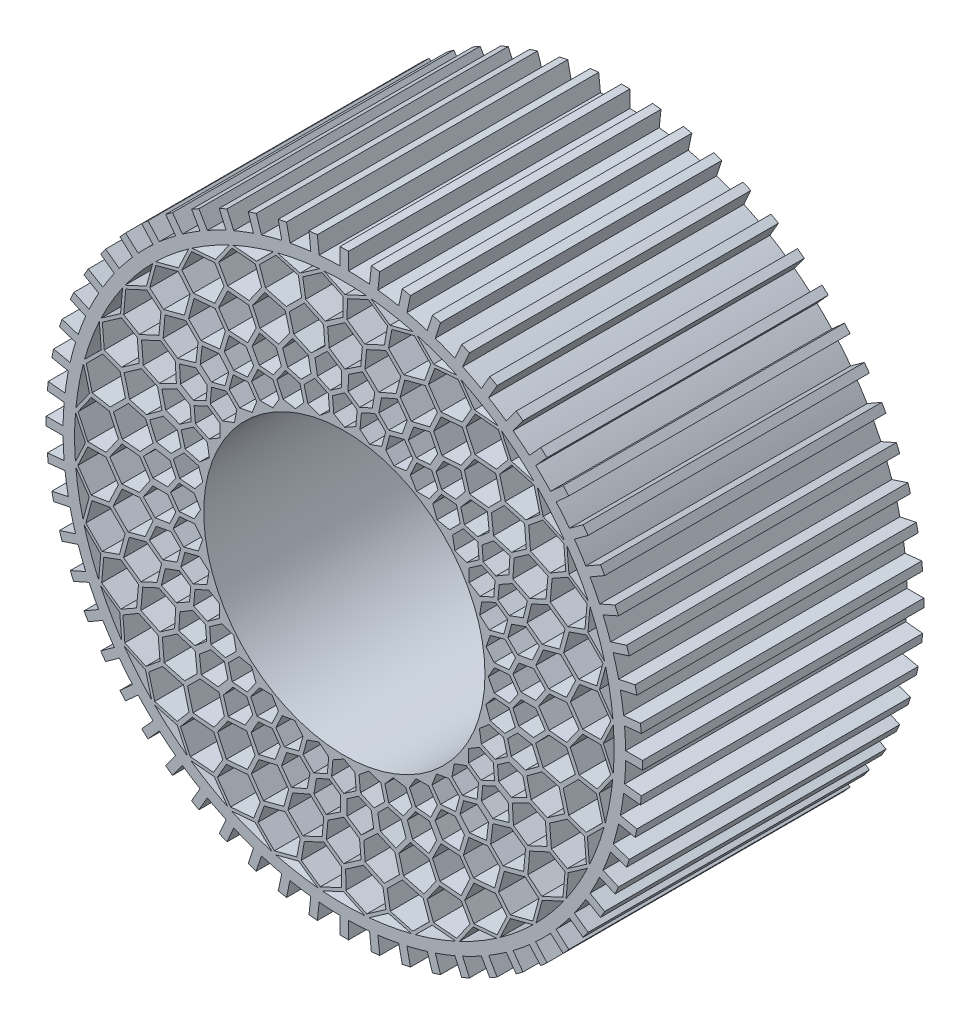
SolidWorks part; units mm, degrees
ref_plane "Front Plane" through (0, 0, 0) normal (0, 0, 1) x (1, 0, 0)
ref_plane "Top Plane" through (0, 0, 0) normal (0, 1, 0) x (1, 0, 0)
ref_plane "Right Plane" through (0, 0, 0) normal (1, 0, 0) x (0, 0, -1)
sketch "Sketch1" plane through (0, 0, 0) normal (0, 0, 1) x (1, 0, 0)
  line L0 (0, 0) -> (0, 101.6)
  line L1 (0, 101.6) -> (0, 107.696) construction
  line L2 (-1.524, 107.696) -> (1.524, 107.696)
  line L3 (1.524, 107.696) -> (1.524, 101.5886)
  line L4 (-1.524, 107.696) -> (-1.524, 101.5886)
  line L5 (10.6201, 101.0434) -> (11.2573, 107.106) construction
  line L6 (9.7416, 107.2653) -> (12.7729, 106.9467)
  line L7 (9.7416, 107.2653) -> (9.1032, 101.1914)
  line L8 (12.7729, 106.9467) -> (12.1345, 100.8728)
  line L9 (21.1238, 99.3798) -> (22.3913, 105.3426) construction
  line L10 (20.9006, 105.6594) -> (23.882, 105.0257)
  line L11 (20.9006, 105.6594) -> (19.6308, 99.6855)
  line L12 (23.882, 105.0257) -> (22.6121, 99.0518)
  line L13 (31.3961, 96.6273) -> (33.2799, 102.425) construction
  line L14 (31.8305, 102.8959) -> (34.7293, 101.954)
  line L15 (31.8305, 102.8959) -> (29.9432, 97.0874)
  line L16 (34.7293, 101.954) -> (32.842, 96.1455)
  line L17 (41.3244, 92.8162) -> (43.8039, 98.3852) construction
  line L18 (42.4117, 99.0051) -> (45.1962, 97.7653)
  line L19 (42.4117, 99.0051) -> (39.9276, 93.4256)
  line L20 (45.1962, 97.7653) -> (42.712, 92.1859)
  line L21 (50.8, 87.9882) -> (53.848, 93.2675) construction
  line L22 (52.5282, 94.0295) -> (55.1678, 92.5055)
  line L23 (52.5282, 94.0295) -> (49.4745, 88.7403)
  line L24 (55.1678, 92.5055) -> (52.1141, 87.2163)
  line L25 (59.719, 82.1961) -> (63.3021, 87.1279) construction
  line L26 (62.0692, 88.0237) -> (64.5351, 86.2321)
  line L27 (62.0692, 88.0237) -> (58.4793, 83.0827)
  line L28 (64.5351, 86.2321) -> (60.9452, 81.2911)
  line L29 (67.9837, 75.5035) -> (72.0627, 80.0337) construction
  line L30 (70.9301, 81.0535) -> (73.1952, 79.014)
  line L31 (70.9301, 81.0535) -> (66.8435, 76.5148)
  line L32 (73.1952, 79.014) -> (69.1086, 74.4753)
  line L33 (75.5035, 67.9837) -> (80.0337, 72.0627) construction
  line L34 (79.014, 73.1952) -> (81.0535, 70.9301)
  line L35 (79.014, 73.1952) -> (74.4753, 69.1086)
  line L36 (81.0535, 70.9301) -> (76.5148, 66.8435)
  line L37 (82.1961, 59.719) -> (87.1279, 63.3021) construction
  line L38 (86.2321, 64.5351) -> (88.0237, 62.0692)
  line L39 (86.2321, 64.5351) -> (81.2911, 60.9452)
  line L40 (88.0237, 62.0692) -> (83.0827, 58.4793)
  line L41 (87.9882, 50.8) -> (93.2675, 53.848) construction
  line L42 (92.5055, 55.1678) -> (94.0295, 52.5282)
  line L43 (92.5055, 55.1678) -> (87.2163, 52.1141)
  line L44 (94.0295, 52.5282) -> (88.7403, 49.4745)
  line L45 (92.8162, 41.3244) -> (98.3852, 43.8039) construction
  line L46 (97.7653, 45.1962) -> (99.0051, 42.4117)
  line L47 (97.7653, 45.1962) -> (92.1859, 42.712)
  line L48 (99.0051, 42.4117) -> (93.4256, 39.9276)
  line L49 (96.6273, 31.3961) -> (102.425, 33.2799) construction
  line L50 (101.954, 34.7293) -> (102.8959, 31.8305)
  line L51 (101.954, 34.7293) -> (96.1455, 32.842)
  line L52 (102.8959, 31.8305) -> (97.0874, 29.9432)
  line L53 (99.3798, 21.1238) -> (105.3426, 22.3913) construction
  line L54 (105.0257, 23.882) -> (105.6594, 20.9006)
  line L55 (105.0257, 23.882) -> (99.0518, 22.6121)
  line L56 (105.6594, 20.9006) -> (99.6855, 19.6308)
  line L57 (101.0434, 10.6201) -> (107.106, 11.2573) construction
  line L58 (106.9467, 12.7729) -> (107.2653, 9.7416)
  line L59 (106.9467, 12.7729) -> (100.8728, 12.1345)
  line L60 (107.2653, 9.7416) -> (101.1914, 9.1032)
  line L61 (101.6, 0) -> (107.696, 0) construction
  line L62 (107.696, 1.524) -> (107.696, -1.524)
  line L63 (107.696, 1.524) -> (101.5886, 1.524)
  line L64 (107.696, -1.524) -> (101.5886, -1.524)
  line L65 (101.0434, -10.6201) -> (107.106, -11.2573) construction
  line L66 (107.2653, -9.7416) -> (106.9467, -12.7729)
  line L67 (107.2653, -9.7416) -> (101.1914, -9.1032)
  line L68 (106.9467, -12.7729) -> (100.8728, -12.1345)
  line L69 (99.3798, -21.1238) -> (105.3426, -22.3913) construction
  line L70 (105.6594, -20.9006) -> (105.0257, -23.882)
  line L71 (105.6594, -20.9006) -> (99.6855, -19.6308)
  line L72 (105.0257, -23.882) -> (99.0518, -22.6121)
  line L73 (96.6273, -31.3961) -> (102.425, -33.2799) construction
  line L74 (102.8959, -31.8305) -> (101.954, -34.7293)
  line L75 (102.8959, -31.8305) -> (97.0874, -29.9432)
  line L76 (101.954, -34.7293) -> (96.1455, -32.842)
  line L77 (92.8162, -41.3244) -> (98.3852, -43.8039) construction
  line L78 (99.0051, -42.4117) -> (97.7653, -45.1962)
  line L79 (99.0051, -42.4117) -> (93.4256, -39.9276)
  line L80 (97.7653, -45.1962) -> (92.1859, -42.712)
  line L81 (87.9882, -50.8) -> (93.2675, -53.848) construction
  line L82 (94.0295, -52.5282) -> (92.5055, -55.1678)
  line L83 (94.0295, -52.5282) -> (88.7403, -49.4745)
  line L84 (92.5055, -55.1678) -> (87.2163, -52.1141)
  line L85 (82.1961, -59.719) -> (87.1279, -63.3021) construction
  line L86 (88.0237, -62.0692) -> (86.2321, -64.5351)
  line L87 (88.0237, -62.0692) -> (83.0827, -58.4793)
  line L88 (86.2321, -64.5351) -> (81.2911, -60.9452)
  line L89 (75.5035, -67.9837) -> (80.0337, -72.0627) construction
  line L90 (81.0535, -70.9301) -> (79.014, -73.1952)
  line L91 (81.0535, -70.9301) -> (76.5148, -66.8435)
  line L92 (79.014, -73.1952) -> (74.4753, -69.1086)
  line L93 (67.9837, -75.5035) -> (72.0627, -80.0337) construction
  line L94 (73.1952, -79.014) -> (70.9301, -81.0535)
  line L95 (73.1952, -79.014) -> (69.1086, -74.4753)
  line L96 (70.9301, -81.0535) -> (66.8435, -76.5148)
  line L97 (59.719, -82.1961) -> (63.3021, -87.1279) construction
  line L98 (64.5351, -86.2321) -> (62.0692, -88.0237)
  line L99 (64.5351, -86.2321) -> (60.9452, -81.2911)
  line L100 (62.0692, -88.0237) -> (58.4793, -83.0827)
  line L101 (50.8, -87.9882) -> (53.848, -93.2675) construction
  line L102 (55.1678, -92.5055) -> (52.5282, -94.0295)
  line L103 (55.1678, -92.5055) -> (52.1141, -87.2163)
  line L104 (52.5282, -94.0295) -> (49.4745, -88.7403)
  line L105 (41.3244, -92.8162) -> (43.8039, -98.3852) construction
  line L106 (45.1962, -97.7653) -> (42.4117, -99.0051)
  line L107 (45.1962, -97.7653) -> (42.712, -92.1859)
  line L108 (42.4117, -99.0051) -> (39.9276, -93.4256)
  line L109 (31.3961, -96.6273) -> (33.2799, -102.425) construction
  line L110 (34.7293, -101.954) -> (31.8305, -102.8959)
  line L111 (34.7293, -101.954) -> (32.842, -96.1455)
  line L112 (31.8305, -102.8959) -> (29.9432, -97.0874)
  line L113 (21.1238, -99.3798) -> (22.3913, -105.3426) construction
  line L114 (23.882, -105.0257) -> (20.9006, -105.6594)
  line L115 (23.882, -105.0257) -> (22.6121, -99.0518)
  line L116 (20.9006, -105.6594) -> (19.6308, -99.6855)
  line L117 (10.6201, -101.0434) -> (11.2573, -107.106) construction
  line L118 (12.7729, -106.9467) -> (9.7416, -107.2653)
  line L119 (12.7729, -106.9467) -> (12.1345, -100.8728)
  line L120 (9.7416, -107.2653) -> (9.1032, -101.1914)
  line L121 (0, -101.6) -> (0, -107.696) construction
  line L122 (1.524, -107.696) -> (-1.524, -107.696)
  line L123 (1.524, -107.696) -> (1.524, -101.5886)
  line L124 (-1.524, -107.696) -> (-1.524, -101.5886)
  line L125 (-10.6201, -101.0434) -> (-11.2573, -107.106) construction
  line L126 (-9.7416, -107.2653) -> (-12.7729, -106.9467)
  line L127 (-9.7416, -107.2653) -> (-9.1032, -101.1914)
  line L128 (-12.7729, -106.9467) -> (-12.1345, -100.8728)
  line L129 (-21.1238, -99.3798) -> (-22.3913, -105.3426) construction
  line L130 (-20.9006, -105.6594) -> (-23.882, -105.0257)
  line L131 (-20.9006, -105.6594) -> (-19.6308, -99.6855)
  line L132 (-23.882, -105.0257) -> (-22.6121, -99.0518)
  line L133 (-31.3961, -96.6273) -> (-33.2799, -102.425) construction
  line L134 (-31.8305, -102.8959) -> (-34.7293, -101.954)
  line L135 (-31.8305, -102.8959) -> (-29.9432, -97.0874)
  line L136 (-34.7293, -101.954) -> (-32.842, -96.1455)
  line L137 (-41.3244, -92.8162) -> (-43.8039, -98.3852) construction
  line L138 (-42.4117, -99.0051) -> (-45.1962, -97.7653)
  line L139 (-42.4117, -99.0051) -> (-39.9276, -93.4256)
  line L140 (-45.1962, -97.7653) -> (-42.712, -92.1859)
  line L141 (-50.8, -87.9882) -> (-53.848, -93.2675) construction
  line L142 (-52.5282, -94.0295) -> (-55.1678, -92.5055)
  line L143 (-52.5282, -94.0295) -> (-49.4745, -88.7403)
  line L144 (-55.1678, -92.5055) -> (-52.1141, -87.2163)
  line L145 (-59.719, -82.1961) -> (-63.3021, -87.1279) construction
  line L146 (-62.0692, -88.0237) -> (-64.5351, -86.2321)
  line L147 (-62.0692, -88.0237) -> (-58.4793, -83.0827)
  line L148 (-64.5351, -86.2321) -> (-60.9452, -81.2911)
  line L149 (-67.9837, -75.5035) -> (-72.0627, -80.0337) construction
  line L150 (-70.9301, -81.0535) -> (-73.1952, -79.014)
  line L151 (-70.9301, -81.0535) -> (-66.8435, -76.5148)
  line L152 (-73.1952, -79.014) -> (-69.1086, -74.4753)
  line L153 (-75.5035, -67.9837) -> (-80.0337, -72.0627) construction
  line L154 (-79.014, -73.1952) -> (-81.0535, -70.9301)
  line L155 (-79.014, -73.1952) -> (-74.4753, -69.1086)
  line L156 (-81.0535, -70.9301) -> (-76.5148, -66.8435)
  line L157 (-82.1961, -59.719) -> (-87.1279, -63.3021) construction
  line L158 (-86.2321, -64.5351) -> (-88.0237, -62.0692)
  line L159 (-86.2321, -64.5351) -> (-81.2911, -60.9452)
  line L160 (-88.0237, -62.0692) -> (-83.0827, -58.4793)
  line L161 (-87.9882, -50.8) -> (-93.2675, -53.848) construction
  line L162 (-92.5055, -55.1678) -> (-94.0295, -52.5282)
  line L163 (-92.5055, -55.1678) -> (-87.2163, -52.1141)
  line L164 (-94.0295, -52.5282) -> (-88.7403, -49.4745)
  line L165 (-92.8162, -41.3244) -> (-98.3852, -43.8039) construction
  line L166 (-97.7653, -45.1962) -> (-99.0051, -42.4117)
  line L167 (-97.7653, -45.1962) -> (-92.1859, -42.712)
  line L168 (-99.0051, -42.4117) -> (-93.4256, -39.9276)
  line L169 (-96.6273, -31.3961) -> (-102.425, -33.2799) construction
  line L170 (-101.954, -34.7293) -> (-102.8959, -31.8305)
  line L171 (-101.954, -34.7293) -> (-96.1455, -32.842)
  line L172 (-102.8959, -31.8305) -> (-97.0874, -29.9432)
  line L173 (-99.3798, -21.1238) -> (-105.3426, -22.3913) construction
  line L174 (-105.0257, -23.882) -> (-105.6594, -20.9006)
  line L175 (-105.0257, -23.882) -> (-99.0518, -22.6121)
  line L176 (-105.6594, -20.9006) -> (-99.6855, -19.6308)
  line L177 (-101.0434, -10.6201) -> (-107.106, -11.2573) construction
  line L178 (-106.9467, -12.7729) -> (-107.2653, -9.7416)
  line L179 (-106.9467, -12.7729) -> (-100.8728, -12.1345)
  line L180 (-107.2653, -9.7416) -> (-101.1914, -9.1032)
  line L181 (-101.6, 0) -> (-107.696, 0) construction
  line L182 (-107.696, -1.524) -> (-107.696, 1.524)
  line L183 (-107.696, -1.524) -> (-101.5886, -1.524)
  line L184 (-107.696, 1.524) -> (-101.5886, 1.524)
  line L185 (-101.0434, 10.6201) -> (-107.106, 11.2573) construction
  line L186 (-107.2653, 9.7416) -> (-106.9467, 12.7729)
  line L187 (-107.2653, 9.7416) -> (-101.1914, 9.1032)
  line L188 (-106.9467, 12.7729) -> (-100.8728, 12.1345)
  line L189 (-99.3798, 21.1238) -> (-105.3426, 22.3913) construction
  line L190 (-105.6594, 20.9006) -> (-105.0257, 23.882)
  line L191 (-105.6594, 20.9006) -> (-99.6855, 19.6308)
  line L192 (-105.0257, 23.882) -> (-99.0518, 22.6121)
  line L193 (-96.6273, 31.3961) -> (-102.425, 33.2799) construction
  line L194 (-102.8959, 31.8305) -> (-101.954, 34.7293)
  line L195 (-102.8959, 31.8305) -> (-97.0874, 29.9432)
  line L196 (-101.954, 34.7293) -> (-96.1455, 32.842)
  line L197 (-92.8162, 41.3244) -> (-98.3852, 43.8039) construction
  line L198 (-99.0051, 42.4117) -> (-97.7653, 45.1962)
  line L199 (-99.0051, 42.4117) -> (-93.4256, 39.9276)
  line L200 (-97.7653, 45.1962) -> (-92.1859, 42.712)
  line L201 (-87.9882, 50.8) -> (-93.2675, 53.848) construction
  line L202 (-94.0295, 52.5282) -> (-92.5055, 55.1678)
  line L203 (-94.0295, 52.5282) -> (-88.7403, 49.4745)
  line L204 (-92.5055, 55.1678) -> (-87.2163, 52.1141)
  line L205 (-82.1961, 59.719) -> (-87.1279, 63.3021) construction
  line L206 (-88.0237, 62.0692) -> (-86.2321, 64.5351)
  line L207 (-88.0237, 62.0692) -> (-83.0827, 58.4793)
  line L208 (-86.2321, 64.5351) -> (-81.2911, 60.9452)
  line L209 (-75.5035, 67.9837) -> (-80.0337, 72.0627) construction
  line L210 (-81.0535, 70.9301) -> (-79.014, 73.1952)
  line L211 (-81.0535, 70.9301) -> (-76.5148, 66.8435)
  line L212 (-79.014, 73.1952) -> (-74.4753, 69.1086)
  line L213 (-67.9837, 75.5035) -> (-72.0627, 80.0337) construction
  line L214 (-73.1952, 79.014) -> (-70.9301, 81.0535)
  line L215 (-73.1952, 79.014) -> (-69.1086, 74.4753)
  line L216 (-70.9301, 81.0535) -> (-66.8435, 76.5148)
  line L217 (-59.719, 82.1961) -> (-63.3021, 87.1279) construction
  line L218 (-64.5351, 86.2321) -> (-62.0692, 88.0237)
  line L219 (-64.5351, 86.2321) -> (-60.9452, 81.2911)
  line L220 (-62.0692, 88.0237) -> (-58.4793, 83.0827)
  line L221 (-50.8, 87.9882) -> (-53.848, 93.2675) construction
  line L222 (-55.1678, 92.5055) -> (-52.5282, 94.0295)
  line L223 (-55.1678, 92.5055) -> (-52.1141, 87.2163)
  line L224 (-52.5282, 94.0295) -> (-49.4745, 88.7403)
  line L225 (-41.3244, 92.8162) -> (-43.8039, 98.3852) construction
  line L226 (-45.1962, 97.7653) -> (-42.4117, 99.0051)
  line L227 (-45.1962, 97.7653) -> (-42.712, 92.1859)
  line L228 (-42.4117, 99.0051) -> (-39.9276, 93.4256)
  line L229 (-31.3961, 96.6273) -> (-33.2799, 102.425) construction
  line L230 (-34.7293, 101.954) -> (-31.8305, 102.8959)
  line L231 (-34.7293, 101.954) -> (-32.842, 96.1455)
  line L232 (-31.8305, 102.8959) -> (-29.9432, 97.0874)
  line L233 (-21.1238, 99.3798) -> (-22.3913, 105.3426) construction
  line L234 (-23.882, 105.0257) -> (-20.9006, 105.6594)
  line L235 (-23.882, 105.0257) -> (-22.6121, 99.0518)
  line L236 (-20.9006, 105.6594) -> (-19.6308, 99.6855)
  line L237 (-10.6201, 101.0434) -> (-11.2573, 107.106) construction
  line L238 (-12.7729, 106.9467) -> (-9.7416, 107.2653)
  line L239 (-12.7729, 106.9467) -> (-12.1345, 100.8728)
  line L240 (-9.7416, 107.2653) -> (-9.1032, 101.1914)
  circle A0 centre (0, 0) radius 101.6
  circle A1 centre (0, 0) radius 50.8
  point P9 (0, 107.696)
  point P367 (0, 0)
  dimension "D1" = 203.2
  dimension "D2" = 101.6
  dimension "D3" = 6.096
  dimension "D4" = 3.048
  dimension "D5" = 60
extrude "Boss-Extrude3" add sketch "Sketch1" along normal blind 101.6 contours A0 L88 L86 L87 | A0 L84 L82 L83 | A0 L80 L78 L79 | A0 L76 L74 L75 | A0 L72 L70 L71 | A0 L68 L66 L67 | A0 L64 L62 L63 | A0 L60 L58 L59 | A0 L52 L50 L51 | A0 L56 L54 L55 | A0 L20 L18 L19 | A0 L24 L22 L23 | A0 L28 L26 L27 | A0 L32 L30 L31 | A0 L36 L34 L35 | A0 L40 L38 L39 | A0 L44 L42 L43 | A0 L48 L46 L47 | A0 L3 L2 L4 | A0 L8 L6 L7 | A0 L12 L10 L11 | A0 L16 L14 L15 | A0 L224 L222 L223 | A0 L228 L226 L227 | A0 L232 L230 L231 | A0 L236 L234 L235 | A0 L240 L238 L239 | A1 A0 | A0 L208 L206 L207 | A0 L212 L210 L211 | A0 L216 L214 L215 | A0 L220 L218 L219 | A0 L196 L194 L195 | A0 L200 L198 L199 | A0 L204 L202 L203 | A0 L176 L174 L175 | A0 L180 L178 L179 | A0 L184 L182 L183 | A0 L188 L186 L187 | A0 L192 L190 L191 | A0 L152 L150 L151 | A0 L156 L154 L155 | A0 L160 L158 L159 | A0 L164 L162 L163 | A0 L172 L170 L171 | A0 L168 L166 L167 | A0 L148 L146 L147 | A0 L144 L142 L143 | A0 L140 L138 L139 | A0 L136 L134 L135 | A0 L132 L130 L131 | A0 L124 L122 L123 | A0 L128 L126 L127 | A0 L116 L114 L115 | A0 L112 L110 L111 | A0 L108 L106 L107 | A0 L104 L102 L103 | A0 L100 L98 L99 | A0 L96 L94 L95 | A0 L92 L90 L91 | A0 L120 L118 L119 region at (0.7405, 98.7235, 0) region at (0, 104.6461, 0) region at (10.9385, 104.0728, 0) region at (-10.9385, 104.0728, 0) region at (21.7571, 102.3593, 0) region at (-21.7571, 102.3593, 0) region at (32.3374, 99.5243, 0) region at (-32.3374, 99.5243, 0) region at (42.5634, 95.599, 0) region at (-42.5634, 95.599, 0) region at (52.323, 90.6262, 0) region at (-52.323, 90.6262, 0) region at (61.5094, 84.6605, 0) region at (-61.5094, 84.6605, 0) region at (70.0219, 77.7672, 0) region at (-70.0219, 77.7672, 0) region at (77.7672, 70.0219, 0) region at (-77.7672, 70.0219, 0) region at (84.6605, 61.5094, 0) region at (-84.6605, 61.5094, 0) region at (90.6262, 52.323, 0) region at (-90.6262, 52.323, 0) region at (95.599, 42.5634, 0) region at (-95.599, 42.5634, 0) region at (99.5243, 32.3374, 0) region at (-99.5243, 32.3374, 0) region at (102.3593, 21.7571, 0) region at (-102.3593, 21.7571, 0) region at (104.0728, 10.9385, 0) region at (-104.0728, 10.9385, 0) region at (104.6461, 0, 0) region at (-104.6461, 0, 0) region at (-104.0728, -10.9385, 0) region at (104.0728, -10.9385, 0) region at (-102.3593, -21.7571, 0) region at (102.3593, -21.7571, 0) region at (-99.5243, -32.3374, 0) region at (99.5243, -32.3374, 0) region at (-95.599, -42.5634, 0) region at (95.599, -42.5634, 0) region at (-90.6262, -52.323, 0) region at (90.6262, -52.323, 0) region at (-84.6605, -61.5094, 0) region at (84.6605, -61.5094, 0) region at (-77.7672, -70.0219, 0) region at (77.7672, -70.0219, 0) region at (-70.0219, -77.7672, 0) region at (70.0219, -77.7672, 0) region at (-61.5094, -84.6605, 0) region at (61.5094, -84.6605, 0) region at (-52.323, -90.6262, 0) region at (52.323, -90.6262, 0) region at (-42.5634, -95.599, 0) region at (42.5634, -95.599, 0) region at (-32.3374, -99.5243, 0) region at (32.3374, -99.5243, 0) region at (-21.7571, -102.3593, 0) region at (21.7571, -102.3593, 0) region at (-10.9385, -104.0728, 0) region at (10.9385, -104.0728, 0)
sketch "Sketch2" plane through (0, 0, 101.6) normal (0, 0, 1) x (1, 0, 0)
  line L0 (-13.9549, 84.9459) -> (-15.0228, 91.4463)
  line L1 (-0.4947, 86.0831) -> (-0.5325, 92.6706)
  line L2 (0, 0) -> (-14.8872, 90.6204) construction
  line L3 (-6.8965, 81.6288) -> (-0.4947, 86.0831)
  line L5 (-0.5325, 92.6706) -> (-8.1311, 96.2415)
  line L6 (-8.1311, 96.2415) -> (-15.0228, 91.4463)
  line L8 (-13.9549, 84.9459) -> (-6.8965, 81.6288)
  line L27 (0, 0) -> (-0.5212, 90.6913) construction
  line L28 (0, 0) -> (-10.1703, 120.3782)
  line L29 (-13.8532, 88.5418) -> (-13.107, 79.7091) [skipped]
  line L30 (-0.4578, 80.8465) -> (-1.0751, 88.1528) [skipped]
  line L37 (0, 0) -> (0.2918, 97.9183)
  line L38 (-9.7149, 63.053) -> (-10.5884, 68.3702)
  line L50 (-5.4859, 73.9839) -> (0.2092, 70.1809)
  line L55 (-5.1457, 60.9058) -> (-1.0016, 63.7892)
  line L56 (-5.4859, 73.9839) -> (-6.0261, 80.3778)
  line L57 (5.9268, 73.9499) -> (0.2092, 70.1809)
  line L58 (5.9268, 73.9499) -> (6.5051, 80.3405)
  line L59 (-7.4429, 97.1469) -> (0.2787, 93.5182)
  line L60 (-6.0261, 80.3778) -> (0.2526, 84.7464)
  line L61 (6.5051, 80.3405) -> (0.2526, 84.7464)
  line L62 (0.2787, 93.5182) -> (0.2895, 97.1469)
  line L68 (-9.7149, 63.053) -> (-5.1457, 60.9058)
  line L69 (-6.6398, 67.394) -> (-6.4182, 64.7714) [skipped]
  line L70 (-2.51, 65.0362) -> (-4.6705, 63.533) [skipped]
  line L71 (-4.1253, 62.5092) -> (-6.5073, 63.6286) [skipped]
  line L72 (-4.3452, 62.6277) -> (-4.5668, 65.2503) [skipped]
  line L73 (-1.0016, 63.7892) -> (-1.0325, 69.1775)
  line L74 (-6.1323, 72.583) -> (-1.0325, 69.1775)
  line L75 (-6.1323, 72.583) -> (-10.5884, 68.3702)
  line L76 (-3.8147, 54.2034) -> (-4.2753, 59.6548)
  line L79 (-3.8147, 54.2034) -> (0.1548, 51.9573)
  line L80 (0.1548, 51.9573) -> (4.1377, 54.1797)
  line L84 (0.2787, 93.5182) -> (0.2904, 97.4312)
  line L85 (-8.9615, 97.0186) -> (-15.9648, 92.1459)
  line L86 (-4.2753, 59.6548) -> (0.187, 62.7596)
  line L87 (4.6308, 59.6282) -> (0.187, 62.7596)
  line L88 (-15.9648, 92.1459) -> (-16.6328, 96.0014)
  line L89 (4.1377, 54.1797) -> (4.6308, 59.6282)
  circle A0 centre (-7.5138, 88.9351) radius 6.35 construction
  arc A1 (-7.4429, 97.1469) -> (0.2904, 97.4312) centre (0, 0) cw
  arc A2 (-8.9615, 97.0186) -> (-16.6328, 96.0014) centre (0, 0) ccw
  point P1 (0, 0)
  dimension "D1" = 12.7
  dimension "D5" = 4.5
  dimension "D2" = 0.5
  dimension "D8" = 1.524
  dimension "D6" = 4.5
  dimension "D7" = 0.762
  dimension "D3" = 1.524
  dimension "D9" = 0.635
  dimension "D4" = 1.524
  dimension "D11" = 0.762
  dimension "D10" = 0.762
extrude "Cut-Extrude1" cut sketch "Sketch2" against normal up to surface (101.6 mm away) contours L8 L28 L6 L0 | L28 L3 L1 L5 | L58 L61 L37 L57 | L60 L56 L50 L37 | L74 L28 L55 L73 | L28 L75 L38 L68 | L86 L76 L79 L37 | L80 L89 L87 L37 | L85 L88 A2 | L84 A1 L59 region at (-10.5686, 88.702, 101.6) region at (-4.4632, 89.2179, 101.6) region at (-3.6158, 66.7194, 101.6) region at (-7.6294, 66.3803, 101.6) region at (-2.378, 77.4538, 101.6) region at (2.8396, 77.4383, 101.6) region at (2.0525, 57.2574, 101.6) region at (-1.7112, 57.2686, 101.6) up to face at (0, 0, 0)
pattern_circular "CirPattern1" count 36 over 360 about axis through (0, 0, 101.6) along (0, 0, 1) of "Cut-Extrude1"
